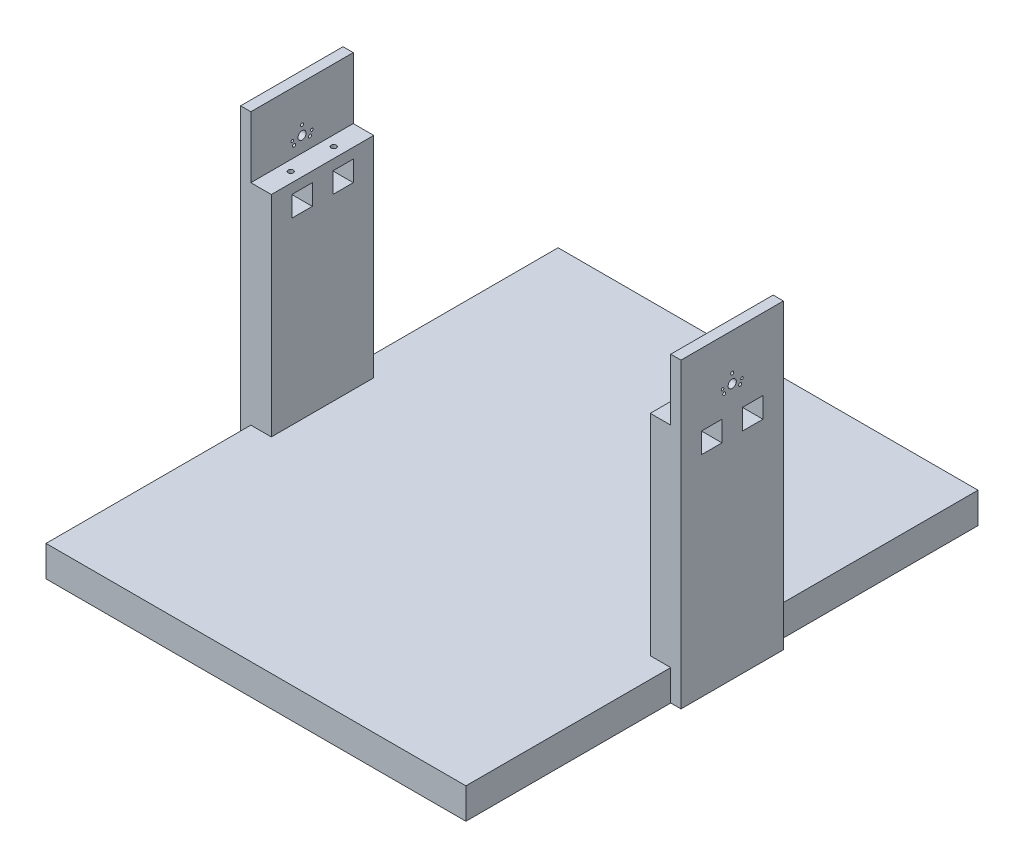
SolidWorks part; units mm, degrees
ref_plane "Plano frontal" through (0, 0, 0) normal (0, 0, 1) x (1, 0, 0)
ref_plane "Plano superior" through (0, 0, 0) normal (0, 1, 0) x (1, 0, 0)
ref_plane "Plano direito" through (0, 0, 0) normal (1, 0, 0) x (0, 0, -1)
sketch "Esboço1" plane through (0, 0, 0) normal (0, 1, 0) x (1, 0, 0)
  line L1 (0, 0) -> (430, 0)
  line L2 (0, 0) -> (0, 500)
  line L3 (0, 500) -> (430, 500)
  line L4 (430, 0) -> (430, 500)
  line L5 (0, 0) -> (20, 0)
  line L6 (0, 0) -> (0, 500)
  line L7 (0, 500) -> (20, 500)
  line L8 (20, 0) -> (20, 500)
  line L9 (430, 0) -> (410, 0)
  line L10 (430, 0) -> (430, 500)
  line L11 (430, 500) -> (410, 500)
  line L12 (410, 0) -> (410, 500)
extrude "Ressalto-extrusão1" add sketch "Esboço1" along normal blind 205 contours L1 L8 L3 L2 region at (10, 0, -250)
extrude "Ressalto-extrusão2" add sketch "Esboço1<3>" along normal blind 30 contours L1 L12 L3 L8 region at (215, 0, -250)
sketch "Esboço1<3>" plane through (0, 0, 0) normal (0, 1, 0) x (1, 0, 0) same geometry as "Esboço1"
sketch "Esboço2" plane through (0, 205, 0) normal (0, 1, 0) x (1, 0, 0)
  line L1 (0, 500) -> (20, 500)
  line L2 (0, 500) -> (0, 0)
  line L3 (0, 0) -> (20, 0)
  line L4 (20, 500) -> (20, 0)
  point P6 (0, 0)
extrude "Ressalto-extrusão4" add sketch "Esboço2" along normal blind 30
sketch "Esboço4" plane through (0, 235, 0) normal (0, 1, 0) x (1, 0, 0)
  line L0 (20, 0) -> (20, 500) construction
  line L1 (20, 250) -> (0, 250)
  line L2 (20, 250) -> (20, 300)
  line L3 (20, 300) -> (0, 300)
  line L4 (0, 250) -> (0, 300)
  line L5 (0, 500) -> (0, 0) construction
  line L7 (20, 250) -> (0, 250)
  line L8 (20, 250) -> (20, 200)
  line L9 (20, 200) -> (0, 200)
  line L10 (0, 250) -> (0, 200)
  point P10 (20, 250)
  line M1 (0, 500) -> (0, 0)
  line M2 (0, 0) -> (20, 0)
  line M3 (20, 0) -> (20, 500)
  line M4 (20, 500) -> (0, 500)
extrude "Corte-extrusão1" cut sketch "Esboço4" against normal blind 205 contours L3 M3 M4 M1 | L9 M3 M1 M2 region at (10, 235, -400) region at (10, 235, -100)
sketch "Esboço6" plane through (0, 235, 0) normal (0, 1, 0) x (1, 0, 0)
  circle A0 centre (10, 271) radius 2.5
  circle A1 centre (10, 229) radius 2.5
extrude "Corte-extrusão3" cut sketch "Esboço6" against normal blind 10
ref_plane "Plano1" through (205, 0, 0) normal (1, 0, 0) x (0, 0, -1)
sketch "Esboço7" plane through (0, 235, 0) normal (0, 1, 0) x (1, 0, 0)
  line L1 (0, 300) -> (-10, 300)
  line L2 (0, 300) -> (0, 200)
  line L3 (0, 200) -> (-10, 200)
  line L4 (-10, 300) -> (-10, 200)
extrude "Ressalto-extrusão6" add sketch "Esboço7" against normal up to surface (235 mm away) and the other way blind 60 up to face at (205, 0, -250)
sketch "Esboço8" plane through (0, 0, 0) normal (1, 0, 0) x (0, 0, -1)
  circle A0 centre (250, 250) radius 4
  circle A1 centre (240.57, 250) radius 1.25
  circle A2 centre (259.53, 250) radius 1.25
  circle A3 centre (250, 259) radius 1.5
  circle A4 centre (257.7942, 245.5) radius 1.5
  circle A5 centre (242.2058, 245.5) radius 1.5
  point P14 (250, 250)
  dimension "D1" = 3
extrude "Corte-extrusão4" cut sketch "Esboço8" against normal up to next
sketch "Esboço9" plane through (-10, 0, 0) normal (-1, 0, 0) x (0, 0, 1)
  line L1 (-280, 225) -> (-260, 225)
  line L2 (-280, 225) -> (-280, 205)
  line L3 (-280, 205) -> (-260, 205)
  line L4 (-260, 225) -> (-260, 205)
  line L5 (-240, 225) -> (-220, 225)
  line L6 (-240, 225) -> (-240, 205)
  line L7 (-240, 205) -> (-220, 205)
  line L8 (-220, 225) -> (-220, 205)
extrude "Corte-extrusão5" cut sketch "Esboço9" against normal up to next
sketch "Esboço10" plane through (0, 0, 0) normal (0, -1, 0) x (1, 0, 0)
  circle A0 centre (50, -50) radius 4
  circle A1 centre (50, -450) radius 4
extrude "Corte-extrusão6" cut sketch "Esboço10" against normal blind 4
mirror "Espelhar1" about plane through (205, 0, 0) normal (1, 0, 0) of "Corte-extrusão6", "Corte-extrusão5", "Corte-extrusão4", "Ressalto-extrusão6", "Corte-extrusão3", "Corte-extrusão1", "Ressalto-extrusão4", "Ressalto-extrusão2", "Ressalto-extrusão1"
